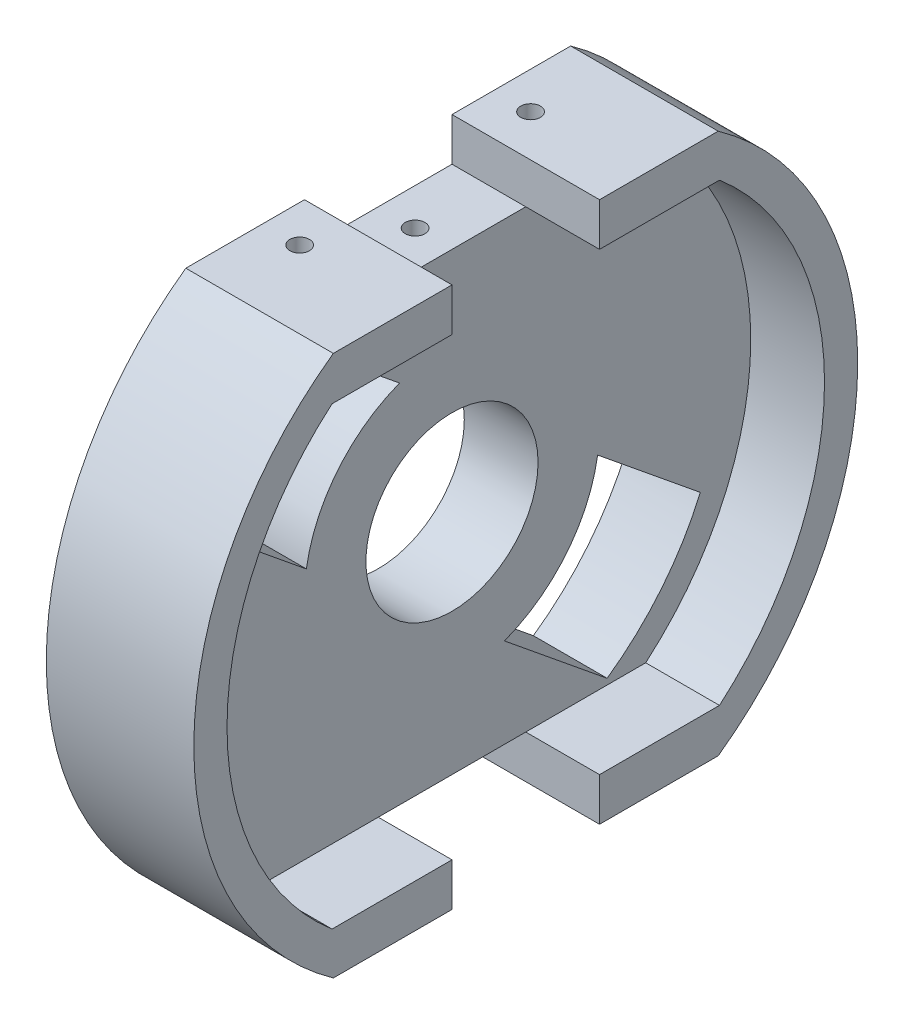
SolidWorks part; units mm, degrees
ref_plane "前视基准面" through (0, 0, 0) normal (0, 0, 1) x (1, 0, 0)
ref_plane "上视基准面" through (0, 0, 0) normal (0, 1, 0) x (1, 0, 0)
ref_plane "右视基准面" through (0, 0, 0) normal (1, 0, 0) x (0, 0, -1)
other "Configuration Table"
sketch "草图1" plane through (0, 0, 0) normal (1, 0, 0) x (0, 0, -1)
  line L0 (-8.7507, 11) -> (13.5, -7.1302)
  line L5 (-13.5, -11) -> (13.5, -11)
  line L6 (-13.5, -11) -> (-13.5, 11)
  line L7 (-13.5, 11) -> (13.5, 11)
  line L8 (13.5, -11) -> (13.5, 11)
  line L9 (-13.5, -11) -> (13.5, 11) construction
  line L10 (-13.5, 11) -> (13.5, -11) construction
  line L11 (-13.5, 7.1302) -> (8.7507, -11)
  circle A0 centre (0, 0) radius 13.5
  circle A1 centre (0, 0) radius 3.5
  circle A2 centre (0, 0) radius 11
  circle A3 centre (0, 0) radius 6
  point P0 (0, 0)
  dimension "D1" = 27
  dimension "D2" = 7
  dimension "D6" = 12
  dimension "D3" = 22
  dimension "D4" = 3
  dimension "D5" = 3
extrude "凸台-拉伸1" add sketch "草图1" along normal blind 3 contours L0 A3 L11 A1 | L0 A3 A1 | L11 A3 L0 A1 | L11 A3 A1 | A3 L0 A2 | A3 L11 A2 | A2 L11 A0 L5 | A2 L7 A0 L0 | A2 L0 A0 L7 | A2 L5 A0 L11 | A2 L0 A0 L11 | A2 L11 A0 L0 region at (0, 10.3718, 5.5817) region at (0, 7.6584, 9.399) region at (0, 5.2546, -4.2815) region at (0, 5.0058, 11.2362) region at (0, 10.783, -3.9131) region at (0, 3.3259, -2.71) region at (0, 2.7417, 3.3648) region at (0, -5.2546, 4.2815) region at (0, -3.3259, 2.71) region at (0, -10.3718, -5.5817) region at (0, -7.6584, -9.399) region at (0, -2.7417, -3.3648)
sketch "草图2" plane through (3, 0, 0) normal (1, 0, 0) x (0, 0, -1)
  line L0 (-7.8262, 11) -> (7.8262, 11) construction
  line L1 (-12.15, -9.25) -> (12.15, -9.25)
  line L2 (-12.15, -9.25) -> (-12.15, 9.25)
  line L3 (-12.15, 9.25) -> (12.15, 9.25)
  line L4 (12.15, -9.25) -> (12.15, 9.25)
  line L5 (-12.15, -9.25) -> (12.15, 9.25) construction
  line L6 (-12.15, 9.25) -> (12.15, -9.25) construction
  line L7 (-13.5, -11) -> (13.5, -11)
  line L8 (-13.5, -11) -> (-13.5, 11)
  line L9 (-13.5, 11) -> (13.5, 11)
  line L10 (13.5, -11) -> (13.5, 11)
  line L11 (-13.5, -11) -> (13.5, 11) construction
  line L12 (-13.5, 11) -> (13.5, -11) construction
  circle A0 centre (0, 0) radius 12.15
  circle A1 centre (0, 0) radius 13.5
  arc A2 (-7.8262, 11) -> (-7.8262, -11) centre (0, 0) ccw construction
  arc M7 (7.8262, -11) -> (7.8262, 11) centre (0, 0) ccw
  line M8 (7.8262, 11) -> (-7.8262, 11)
  arc M9 (-7.8262, 11) -> (-7.8262, -11) centre (0, 0) ccw
  line M10 (-7.8262, -11) -> (7.8262, -11)
  dimension "D1" = 24.3
  dimension "D2" = 18.5
extrude "凸台-拉伸2" add sketch "草图2" along normal blind 3 contours L3 A0 L9 | A0 L3 M8 M9 | A0 L3 L2 M9 | L2 M9 | A0 L2 L1 M9 | A0 L1 M9 M10 | L1 A0 L7 | A0 L1 M10 M7 | A0 L1 L4 M7 | L4 M7 | A0 L4 L3 M7 | A0 L3 M7 M8 region at (3, -6.556, 10.7173) region at (3, -10.1697, 7.7138) region at (3, 0, 12.6924) region at (3, -10.0661, 0) region at (3, 6.556, 10.7173) region at (3, -6.556, -10.7173) region at (3, -10.1697, -7.7138) region at (3, 10.0661, 0) region at (3, 10.1697, 7.7138) region at (3, 0, -12.6924) region at (3, 6.556, -10.7173) region at (3, 10.1697, -7.7138)
sketch "草图3" plane through (0, 11, 0) normal (0, 1, 0) x (1, 0, 0)
  line L6 (0, -7.8262) -> (0, 7.8262) construction
  line L7 (0, 3) -> (6, 3)
  line L8 (0, 3) -> (0, -3)
  line L9 (0, -3) -> (6, -3)
  line L10 (6, 3) -> (6, -3)
  line L11 (6, 7.8262) -> (6, -7.8262) construction
  dimension "D1" = 6
extrude "切除-拉伸1" cut sketch "草图3" against normal up to surface (1.75 mm away) up to face at (4.5, 9.25, 0)
sketch "草图4" plane through (0, 9.25, 0) normal (0, 1, 0) x (1, 0, 0)
  line L0 (0, 0) -> (3, 0) construction
  line L1 (0, -3) -> (0, 3) construction
  line L2 (3, 3) -> (3, -3) construction
  circle A0 centre (1.5, 0) radius 0.4
  point P9 (0, 0)
  dimension "D1" = 0.8
extrude "切除-拉伸2" cut sketch "草图4" against normal blind 3
extrude "切除-拉伸3" cut sketch "草图3<2>" against normal up to surface (22 mm away) from surface up to face at (3, -11, 0) starting at face at (4.5, -9.25, 0)
sketch "草图3<2>" plane through (0, 11, 0) normal (0, 1, 0) x (1, 0, 0) same geometry as "草图3"
extrude "切除-拉伸4" cut sketch "草图4<2>" along normal blind 3 from surface starting at face at (1.5, -9.25, 0)
sketch "草图4<2>" plane through (0, 9.25, 0) normal (0, 1, 0) x (1, 0, 0) same geometry as "草图4"
sketch "草图5" plane through (0, 11, 0) normal (0, 1, 0) x (1, 0, 0)
  line L0 (0, 3) -> (0, 7.8262) construction
  line L1 (1.5, 7.8262) -> (1.5, 4.6957) construction
  line L2 (6, 7.8262) -> (0, 7.8262) construction
  line L4 (1.5, 4.6957) -> (1.5, 1.5652) construction
  line L5 (1.5, 1.5652) -> (1.5, -1.5652) construction
  line L6 (1.5, -1.5652) -> (1.5, -4.6957) construction
  line L7 (1.5, -4.6957) -> (1.5, -7.8262) construction
  line L8 (6, -7.8262) -> (0, -7.8262) construction
  circle A0 centre (1.5, -4.6957) radius 0.4
  circle A1 centre (1.5, 4.6957) radius 0.4
  point P7 (1.5, 4.6349)
  dimension "D2" = 0.8
  dimension "D1" = 1.5
extrude "切除-拉伸5" cut sketch "草图5" against normal blind 2
